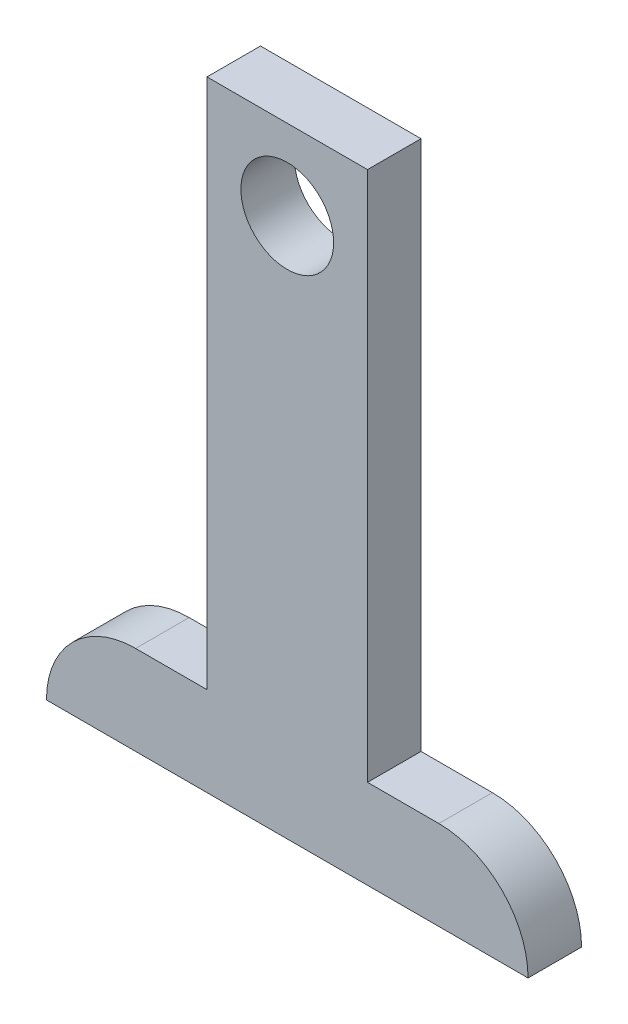
SolidWorks part; units mm, degrees
ref_plane "Plan de face" through (0, 0, 0) normal (0, 0, 1) x (1, 0, 0)
ref_plane "Plan de dessus" through (0, 0, 0) normal (0, 1, 0) x (1, 0, 0)
ref_plane "Plan de droite" through (0, 0, 0) normal (1, 0, 0) x (0, 0, -1)
sketch "Esquisse1" plane through (0, 0, 0) normal (0, 0, 1) x (1, 0, 0)
  line L0 (-9, 0) -> (-18, 0)
  line L1 (-18, 0) -> (-18, -5)
  line L2 (0, 0) -> (0, 29.75)
  line L3 (0, 29.75) -> (-9, 29.75)
  line L4 (-9, 0) -> (-9, 29.75)
  line L5 (-18, -5) -> (9, -5)
  line L6 (9, -5) -> (9, 0)
  line L7 (9, 0) -> (0, 0)
  circle A0 centre (-4.5, 25.25) radius 2.6
  dimension "D4" = 5.2
  dimension "D5" = 4.5
  dimension "D6" = 4.5
  dimension "D1" = 30.25
  dimension "D2" = 9
  dimension "D3" = 5
  dimension "D7" = 9
  dimension "D8" = 9
extrude "Boss.-Extru.1" add sketch "Esquisse1" along normal blind 3
fillet "Congé1" radius 5 1 edges at (-18, 0, 1.5)
fillet "Congé2" radius 5 1 edges at (9, 0, 1.5)
